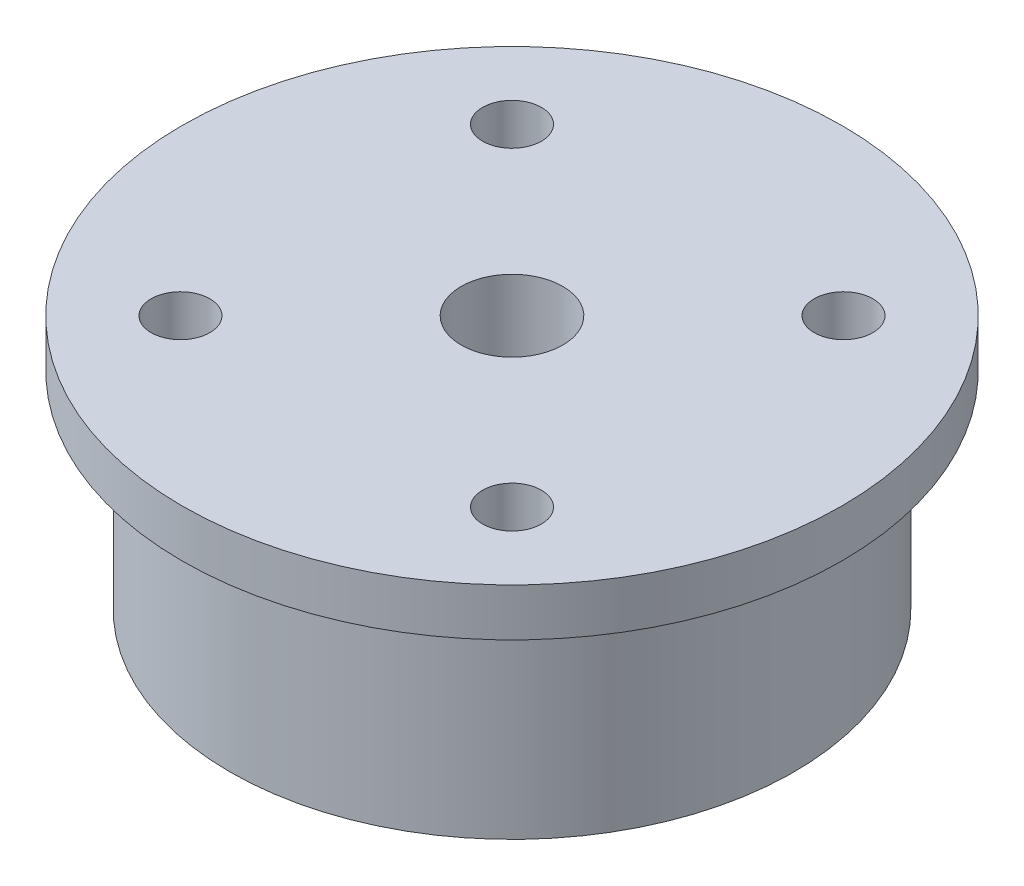
SolidWorks part; units mm, degrees
ref_plane "Front Plane" through (0, 0, 0) normal (0, 0, 1) x (1, 0, 0)
ref_plane "Top Plane" through (0, 0, 0) normal (0, 1, 0) x (1, 0, 0)
ref_plane "Right Plane" through (0, 0, 0) normal (1, 0, 0) x (0, 0, -1)
sketch "Sketch1" plane through (0, 0, 0) normal (0, 1, 0) x (1, 0, 0)
  circle A0 centre (0, 0) radius 1.6
  circle A1 centre (0, 0) radius 8.88
  circle A2 centre (0, 0) radius 10.38
  dimension "D1" = 3.2
  dimension "D2" = 17.76
  dimension "D3" = 20.76
extrude "Boss-Extrude1" add sketch "Sketch1" along normal blind 6.5 contours A1 A0 region at (-8.6288, 0, 0)
extrude "Boss-Extrude2" add sketch "Sketch1<3>" along normal blind 1.5 from surface contours A0 | A2 region at (0, 0, 0) starting at face at (0, 6.5, 1.6)
sketch "Sketch1<3>" plane through (0, 0, 0) normal (0, 1, 0) x (1, 0, 0) same geometry as "Sketch1"
ref_plane "Plane1" through (0, 0, -8.88) normal (0, 0, -1) x (-1, 0, 0)
sketch "Sketch2" plane through (0, 0, -8.88) normal (0, 0, -1) x (-1, 0, 0)
  line L0 (-8.88, 0) -> (8.88, 0) construction
  circle A0 centre (0, 2.75) radius 2.1
  circle A1 centre (0, 2.75) radius 2.35
  dimension "D1" = 4.2
  dimension "D2" = 4.7
  dimension "D3" = 2.75
extrude "Cut-Extrude1" cut sketch "Sketch2" against normal blind 1.2
extrude "Cut-Extrude2" cut sketch "Sketch2<2>" against normal blind 5 contours A0 region at (0, 2.75, -8.88)
sketch "Sketch2<2>" plane through (0, 0, -8.88) normal (0, 0, -1) x (-1, 0, 0) same geometry as "Sketch2"
sketch "Sketch3" plane through (0, 8, 0) normal (0, 1, 0) x (1, 0, 0)
  line L0 (0, 0) -> (-5.2184, 5.2184) construction
  line L1 (0, 0) -> (5.2184, 5.2184) construction
  line L2 (0, 0) -> (5.2184, -5.2184) construction
  line L3 (0, 0) -> (-5.2184, -5.2184) construction
  line L4 (0, 0) -> (0, 7.38) construction
  circle A0 centre (0, 0) radius 7.38 construction
  circle A1 centre (0, 0) radius 10.38 construction
  circle A2 centre (-5.2184, 5.2184) radius 0.925
  circle A3 centre (-5.2184, -5.2184) radius 0.925
  circle A4 centre (5.2184, -5.2184) radius 0.925
  circle A5 centre (5.2184, 5.2184) radius 0.925
  dimension "D1" = 3
  dimension "D6" = 1.85
  dimension "D2" = 90
  dimension "D3" = 90
  dimension "D4" = 90
  dimension "D5" = 45
extrude "Cut-Extrude3" cut sketch "Sketch3" against normal blind 3
